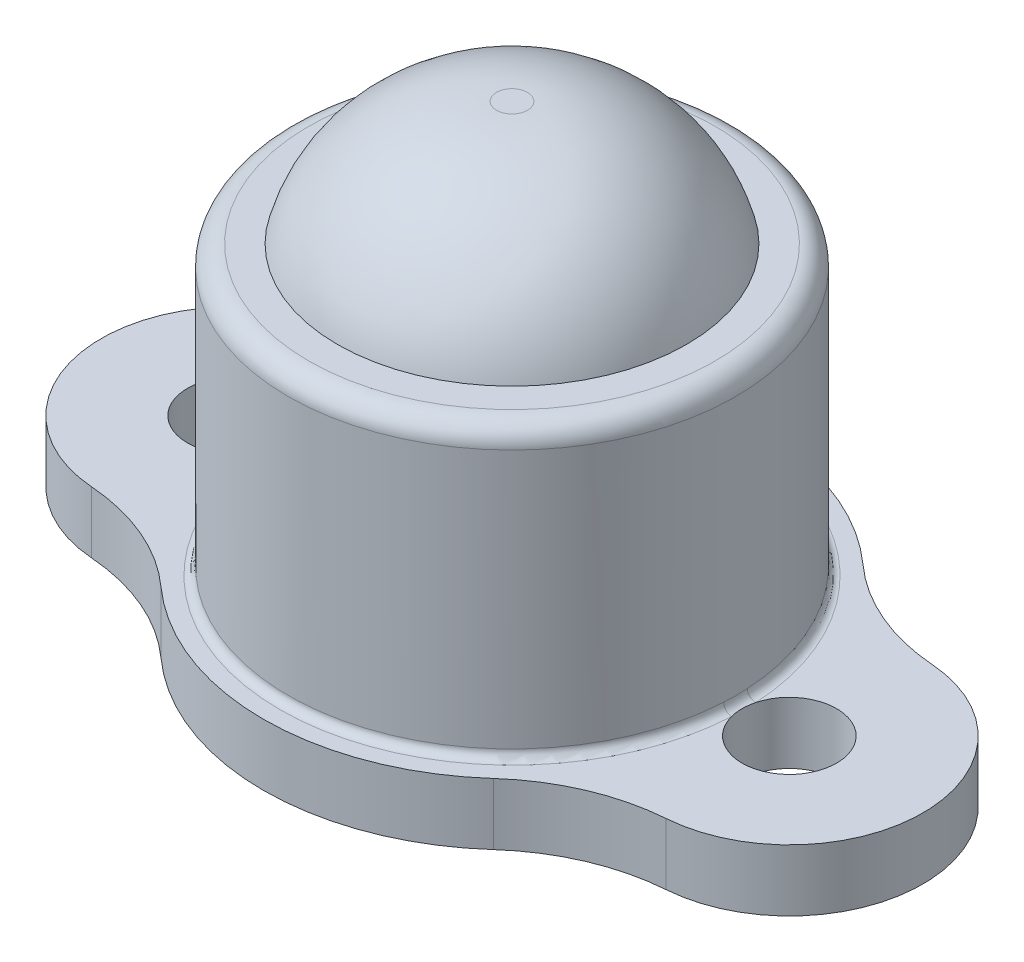
SolidWorks part; units mm, degrees
ref_plane "Front Plane" through (0, 0, 0) normal (0, 0, 1) x (1, 0, 0)
ref_plane "Top Plane" through (0, 0, 0) normal (0, 1, 0) x (1, 0, 0)
ref_plane "Right Plane" through (0, 0, 0) normal (1, 0, 0) x (0, 0, -1)
sketch "Sketch1" plane through (0, 0, 0) normal (0, 1, 0) x (1, 0, 0)
  line L0 (0, 0) -> (0, 6.05) construction
  line L1 (0, 0) -> (-3.5, 0) construction
  arc A0 (-4.0438, -4.5) -> (4.0438, -4.5) centre (0, 0) ccw
  circle A1 centre (0, 0) radius 2.9469
  arc A2 (-6.9932, 3.2409) -> (-6.9932, -3.2409) centre (-6.75, 0) ccw
  arc A3 (6.9932, 3.2409) -> (6.9932, -3.2409) centre (6.75, 0) cw
  arc A4 (-6.9932, -3.2409) -> (-4.0438, -4.5) centre (-7.3651, -8.1959) cw
  arc A5 (-6.9932, 3.2409) -> (-4.0438, 4.5) centre (-7.3651, 8.1959) ccw
  arc A6 (6.9932, -3.2409) -> (4.0438, -4.5) centre (7.3651, -8.1959) ccw
  arc A7 (6.9932, 3.2409) -> (4.0438, 4.5) centre (7.3651, 8.1959) cw
  arc A8 (4.0438, 4.5) -> (-4.0438, 4.5) centre (0, 0) ccw
  dimension "D1" = 12.1
  dimension "D2" = 5.8938
  dimension "D3" = 6.5
  dimension "D5" = 9
  dimension "D4" = 6.75
extrude "Boss-Extrude1" add sketch "Sketch1" along normal blind 1.5 contours A2 A0 | A0 A1 | A3 A0 region at (-5.3224, 0, 3.411)
sketch "Sketch2" plane through (0, 1.5, 0) normal (0, 1, 0) x (1, 0, 0)
  line L0 (0, 0) -> (0, -6.05) construction
  circle A0 centre (-6.75, 0) radius 1.15
  arc A2 (-6.9932, 3.2409) -> (-6.9932, -3.2409) centre (-6.75, 0) ccw construction
  arc A3 (-4.0438, -4.5) -> (4.0438, -4.5) centre (0, 0) ccw construction
  circle A4 centre (6.75, 0) radius 1.15
  dimension "D1" = 2.3
extrude "Cut-Extrude1" cut sketch "Sketch2" against normal up to surface (1.5 mm away) up to face at (0, 0, 2.9469)
sketch "Sketch3" plane through (0, 1.5, 0) normal (0, 1, 0) x (1, 0, 0)
  circle A2 centre (0, 0) radius 5.4469
  circle A3 centre (0, 0) radius 5.4469
  arc A4 (-6.9932, 3.2409) -> (-6.9932, -3.2409) centre (-6.75, 0) ccw
  arc A5 (-6.9932, 3.2409) -> (-4.0438, 4.5) centre (-7.3651, 8.1959) ccw
  arc A6 (6.9932, -3.2409) -> (6.9932, 3.2409) centre (6.75, 0) ccw
  arc A7 (-6.9932, 3.2409) -> (-4.0438, 4.5) centre (-7.3651, 8.1959) ccw
  arc A8 (-6.9932, 3.2409) -> (-6.9932, -3.2409) centre (-6.75, 0) ccw
  arc A9 (-4.0438, -4.5) -> (-6.9932, -3.2409) centre (-7.3651, -8.1959) ccw
  arc A10 (6.9932, -3.2409) -> (6.9932, 3.2409) centre (6.75, 0) ccw
  arc A11 (-4.0438, -4.5) -> (-6.9932, -3.2409) centre (-7.3651, -8.1959) ccw
  arc A18 (-4.0438, -4.5) -> (4.0438, -4.5) centre (0, 0) ccw
  arc A19 (-4.0438, -4.5) -> (4.0438, -4.5) centre (0, 0) ccw
  arc A20 (6.9932, -3.2409) -> (4.0438, -4.5) centre (7.3651, -8.1959) ccw
  arc A21 (6.9932, -3.2409) -> (4.0438, -4.5) centre (7.3651, -8.1959) ccw
  arc A22 (4.0438, 4.5) -> (6.9932, 3.2409) centre (7.3651, 8.1959) ccw
  arc A23 (4.0438, 4.5) -> (6.9932, 3.2409) centre (7.3651, 8.1959) ccw
  arc A24 (4.0438, 4.5) -> (-4.0438, 4.5) centre (0, 0) ccw
  arc A25 (4.0438, 4.5) -> (-4.0438, 4.5) centre (0, 0) ccw
  circle M20 centre (0, 0) radius 2.9469
  dimension "D1" = 0
  dimension "D2" = 2.5
extrude "Boss-Extrude2" add sketch "Sketch3" along normal blind 7 contours A3 M20 region at (-5.2928, 1.5, 0)
sketch "Sketch4" plane through (0, 8.5, 0) normal (0, 1, 0) x (1, 0, 0)
  circle A0 centre (0, 0) radius 4.25
  dimension "D1" = 8.5
extrude "Boss-Extrude3" add sketch "Sketch4" along normal blind 3
fillet "Fillet1" radius 4 1 edges at (0, 11.5, 4.25)
fillet "Fillet2" radius 0.5 1 edges at (0, 8.5, 5.4469)
fillet "Fillet3" radius 0.2 1 edges at (0, 1.5, 5.4469)
